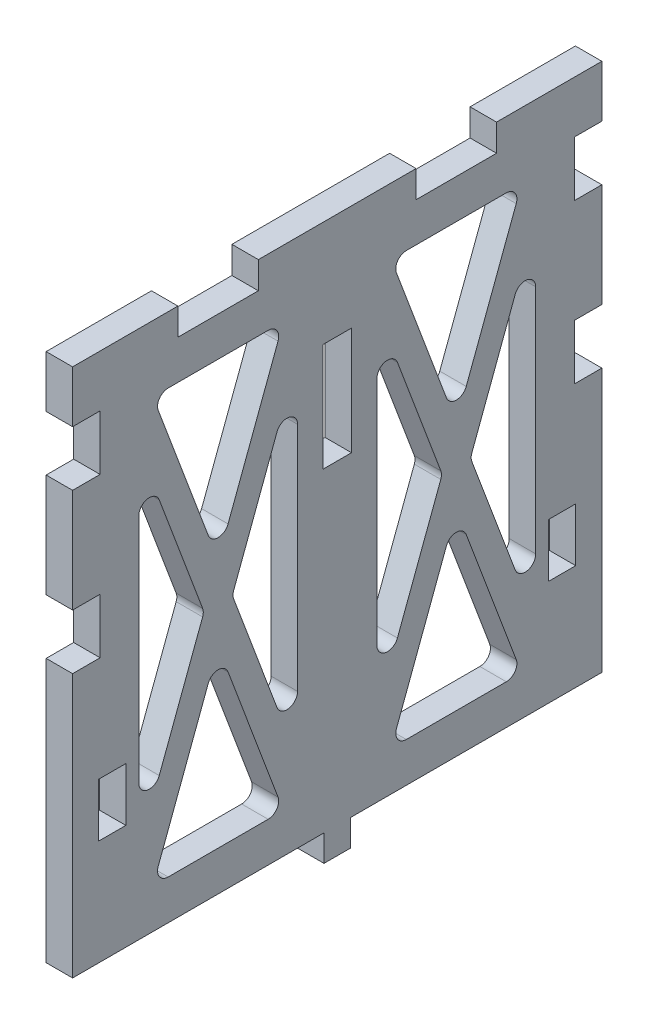
SolidWorks part; units mm, degrees
ref_plane "Front Plane" through (0, 0, 0) normal (0, 0, 1) x (1, 0, 0)
ref_plane "Top Plane" through (0, 0, 0) normal (0, 1, 0) x (1, 0, 0)
ref_plane "Right Plane" through (0, 0, 0) normal (1, 0, 0) x (0, 0, -1)
sketch "Sketch4" plane through (0, 0, 0) normal (1, 0, 0) x (0, 0, -1)
  line L0 (0, 6.35) -> (-60.325, 6.35)
  line L1 (0, 0) -> (6.35, 0)
  line L2 (0, 0) -> (0, 6.35)
  line L3 (0, 6.35) -> (6.35, 6.35) construction
  line L4 (6.35, 0) -> (6.35, 6.35)
  line L5 (6.35, 6.35) -> (66.675, 6.35)
  line L6 (66.675, 6.35) -> (66.675, 32.004)
  line L7 (66.675, 133.35) -> (41.402, 133.35)
  line L8 (-60.325, 133.35) -> (-60.325, 120.904)
  line L9 (3.175, 6.35) -> (3.175, 177.7936) construction
  line L10 (-0.254, 107.95) -> (6.604, 107.95)
  line L11 (0, 107.696) -> (6.35, 107.696) construction
  line L12 (0, 107.696) -> (0, 82.296) construction
  line L13 (0, 82.296) -> (6.35, 82.296) construction
  line L14 (6.35, 107.696) -> (6.35, 82.296) construction
  line L15 (6.604, 107.95) -> (6.604, 82.042)
  line L16 (-0.254, 82.042) -> (6.604, 82.042)
  line L17 (-0.254, 107.95) -> (-0.254, 82.042)
  line L18 (-60.325, 69.85) -> (-53.975, 69.85) construction
  line L19 (-53.975, 69.85) -> (-53.975, 82.55) construction
  line L20 (-53.975, 82.55) -> (-60.325, 82.55) construction
  line L21 (-60.325, 107.95) -> (-53.975, 107.95) construction
  line L22 (-53.975, 107.95) -> (-53.975, 120.65) construction
  line L23 (-53.975, 120.65) -> (-60.325, 120.65) construction
  line L24 (-60.325, 107.696) -> (-60.325, 82.804)
  line L25 (-60.325, 69.596) -> (-60.325, 44.704)
  line L32 (66.675, 120.904) -> (66.675, 133.35)
  line L34 (-60.325, 107.696) -> (-53.721, 107.696)
  line L35 (-53.721, 107.696) -> (-53.721, 120.904)
  line L36 (-53.721, 120.904) -> (-60.325, 120.904)
  line L37 (-60.325, 69.596) -> (-53.721, 69.596)
  line L38 (-53.721, 69.596) -> (-53.721, 82.804)
  line L39 (-53.721, 82.804) -> (-60.325, 82.804)
  line L40 (60.325, 120.65) -> (66.675, 120.65) construction
  line L41 (60.325, 107.95) -> (60.325, 120.65) construction
  line L42 (66.675, 107.95) -> (60.325, 107.95) construction
  line L43 (60.325, 82.55) -> (66.675, 82.55) construction
  line L44 (60.325, 69.85) -> (60.325, 82.55) construction
  line L45 (66.675, 69.85) -> (60.325, 69.85) construction
  line L46 (60.071, 82.804) -> (66.675, 82.804)
  line L47 (60.071, 69.596) -> (60.071, 82.804)
  line L48 (66.675, 69.596) -> (60.071, 69.596)
  line L49 (60.071, 120.904) -> (66.675, 120.904)
  line L50 (60.071, 107.696) -> (60.071, 120.904)
  line L51 (66.675, 107.696) -> (60.071, 107.696)
  line L52 (66.675, 107.696) -> (66.675, 82.804)
  line L53 (-15.748, 133.35) -> (-15.748, 126.873)
  line L59 (-15.875, 133.35) -> (-15.875, 127) construction
  line L60 (-15.875, 127) -> (-34.925, 127) construction
  line L61 (-34.925, 133.35) -> (-34.925, 127) construction
  line L62 (-15.748, 126.873) -> (-35.052, 126.873)
  line L63 (-35.052, 133.35) -> (-35.052, 126.873)
  line L64 (41.402, 133.35) -> (41.402, 126.873)
  line L65 (22.098, 126.873) -> (41.402, 126.873)
  line L66 (22.098, 133.35) -> (22.098, 126.873)
  line L67 (22.098, 133.35) -> (-15.748, 133.35)
  line L68 (-35.052, 133.35) -> (-60.325, 133.35)
  line L69 (66.675, 44.704) -> (66.675, 32.004)
  line L70 (53.975, 44.45) -> (53.975, 31.75) construction
  line L71 (60.325, 31.75) -> (53.975, 31.75) construction
  line L72 (60.325, 44.45) -> (60.325, 31.75) construction
  line L73 (-54.0512, 44.5262) -> (-47.5488, 44.5262)
  line L74 (-53.975, 44.45) -> (-47.625, 44.45) construction
  line L75 (-53.975, 44.45) -> (-53.975, 31.75) construction
  line L76 (0, 32.258) -> (6.35, 32.258) construction
  line L77 (60.325, 44.45) -> (53.975, 44.45) construction
  line L78 (60.4012, 44.5262) -> (60.4012, 31.6738)
  line L79 (60.4012, 31.6738) -> (53.8988, 31.6738)
  line L80 (-53.975, 31.75) -> (-47.625, 31.75) construction
  line L81 (-47.625, 44.45) -> (-47.625, 31.75) construction
  line L82 (-47.5488, 44.5262) -> (-47.5488, 31.6738)
  line L83 (-0.254, 32.512) -> (6.604, 32.512)
  line L84 (-60.325, 32.004) -> (-60.325, 6.35)
  line L85 (66.675, 44.704) -> (66.675, 69.596)
  line L86 (-60.325, 44.704) -> (-60.325, 32.004)
  line L87 (-54.0512, 31.6738) -> (-47.5488, 31.6738)
  line L88 (-54.0512, 44.5262) -> (-54.0512, 31.6738)
  line L89 (53.8988, 44.5262) -> (53.8988, 31.6738)
  line L90 (60.4012, 44.5262) -> (53.8988, 44.5262)
  dimension "D1" = 6.35
  dimension "D2" = 6.35
  dimension "D3" = 60.325
  dimension "D4" = 127
  dimension "D5" = 6.35
  dimension "D6" = 25.4
  dimension "D8" = 25.4
  dimension "D9" = 12.7
  dimension "D10" = 12.7
  dimension "D11" = 6.35
  dimension "D12" = 25.4
  dimension "D15" = 25.4
  dimension "D16" = 19.05
  dimension "D17" = 6.35
  dimension "D19" = 6.35
  dimension "D20" = 12.7
  dimension "D21" = 25.4
  dimension "D22" = 6.35
  dimension "D7" = 0.254
  dimension "D13" = 0.254
  dimension "D14" = 0.254
  dimension "D18" = 0.127
  dimension "D23" = 0.0762
extrude "Boss-Extrude1" add sketch "Sketch4" along normal blind 6.35 contours L85 L48 L47 L46 L52 L51 L50 L49 L32 L7 L64 L65 L66 L67 L53 L62 L63 L68 L8 L36 L35 L34 L24 L39 L38 L37 L25 L73 L84 L0 L2 L1 L4 L5 L6 L78 L17 L10 L15 L16 region at (0, 68.1567, -3.175)
sketch "Sketch5" plane through (6.35, 0, 0) normal (1, 0, 0) x (0, 0, -1)
  line L1 (-44.45, 117.475) -> (50.8, 117.475)
  line L2 (-44.45, 117.475) -> (-44.45, 15.875)
  line L3 (-44.45, 15.875) -> (50.8, 15.875)
  line L4 (50.8, 117.475) -> (50.8, 15.875)
  line L8 (3.175, 117.475) -> (3.175, 15.875) construction
  line L10 (-6.35, 117.475) -> (-6.35, 15.875)
  line L12 (12.7, 117.475) -> (12.7, 15.875)
  line L13 (12.7, 15.875) -> (50.8, 117.475) construction
  line L14 (9.7272, 16.9898) -> (47.8272, 118.5898)
  line L15 (15.6728, 14.7602) -> (53.7728, 116.3602)
  line L16 (50.8, 15.875) -> (12.7, 117.475) construction
  line L17 (47.8272, 14.7602) -> (9.7272, 116.3602)
  line L18 (53.7728, 16.9898) -> (15.6728, 118.5898)
  line L19 (-6.35, 15.875) -> (-44.45, 117.475) construction
  line L20 (-3.3772, 16.9898) -> (-41.4772, 118.5898)
  line L21 (-9.3228, 14.7602) -> (-47.4228, 116.3602)
  line L22 (-44.45, 15.875) -> (-6.35, 117.475) construction
  line L23 (-41.4772, 14.7602) -> (-3.3772, 116.3602)
  line L24 (-47.4228, 16.9898) -> (-9.3228, 118.5898)
  line L25 (66.675, 6.35) -> (66.675, 69.596) construction
  line L26 (66.675, 133.35) -> (41.402, 133.35) construction
  line L27 (-60.325, 69.596) -> (-60.325, 6.35) construction
  line L28 (0, 6.35) -> (-60.325, 6.35) construction
  arc A0 (9.7272, 16.9898) -> (15.6728, 14.7602) centre (12.7, 15.875) ccw
  arc A1 (53.7728, 116.3602) -> (47.8272, 118.5898) centre (50.8, 117.475) ccw
  arc A2 (47.8272, 14.7602) -> (53.7728, 16.9898) centre (50.8, 15.875) ccw
  arc A3 (15.6728, 118.5898) -> (9.7272, 116.3602) centre (12.7, 117.475) ccw
  arc A4 (-3.3772, 16.9898) -> (-9.3228, 14.7602) centre (-6.35, 15.875) cw
  arc A5 (-47.4228, 116.3602) -> (-41.4772, 118.5898) centre (-44.45, 117.475) cw
  arc A6 (-41.4772, 14.7602) -> (-47.4228, 16.9898) centre (-44.45, 15.875) cw
  arc A7 (-9.3228, 118.5898) -> (-3.3772, 116.3602) centre (-6.35, 117.475) cw
  point P18 (31.75, 66.675)
  point P23 (31.75, 66.675)
  point P28 (-25.4, 66.675)
  point P33 (-25.4, 66.675)
  point P40 (55.0942, 131.8089)
  point P43 (45.934, 127.8499)
  dimension "D6" = 3.175
  dimension "D1" = 15.875
  dimension "D2" = 15.875
  dimension "D3" = 15.875
  dimension "D4" = 9.525
  dimension "D5" = 19.05
extrude "Cut-Extrude1" cut sketch "Sketch5" against normal through all contours L2 L24 L21 | L20 L24 L1 | L23 L3 L21 | L14 L17 L12 | L18 L14 L1 | L18 L4 L15 | L3 L17 L15 | L23 L20 L10 region at (6.35, 103.5558, 25.4) region at (6.35, 66.675, 39.2303) region at (6.35, 66.675, 11.5697) region at (6.35, 29.7942, 25.4) region at (6.35, 103.5558, -31.75) region at (6.35, 66.675, -17.9197) region at (6.35, 66.675, -45.5803) region at (6.35, 29.7942, -31.75)
fillet "Fillet1" radius 2.54 24 edges at (3.175, 57.6326, 25.4) (3.175, 15.875, 9.7409) (3.175, 15.875, 41.0591) (3.175, 108.4326, 6.35) (3.175, 24.9174, 6.35) (3.175, 66.675, 22.0091) (3.175, 57.6326, -31.75) (3.175, 15.875, -47.4091) (3.175, 15.875, -16.0909) (3.175, 66.675, -35.1409) (3.175, 108.4326, -50.8) (3.175, 24.9174, -50.8) (3.175, 66.675, 28.7909) (3.175, 24.9174, 44.45) (3.175, 108.4326, 44.45) (3.175, 117.475, -16.0909) (3.175, 117.475, -47.4091) (3.175, 75.7174, -31.75) (3.175, 117.475, 9.7409) (3.175, 75.7174, 25.4) (3.175, 108.4326, -12.7) (3.175, 66.675, -28.3591) (3.175, 24.9174, -12.7) (3.175, 117.475, 41.0591)
fillet "Fillet2" [suppressed] radius 2.54
